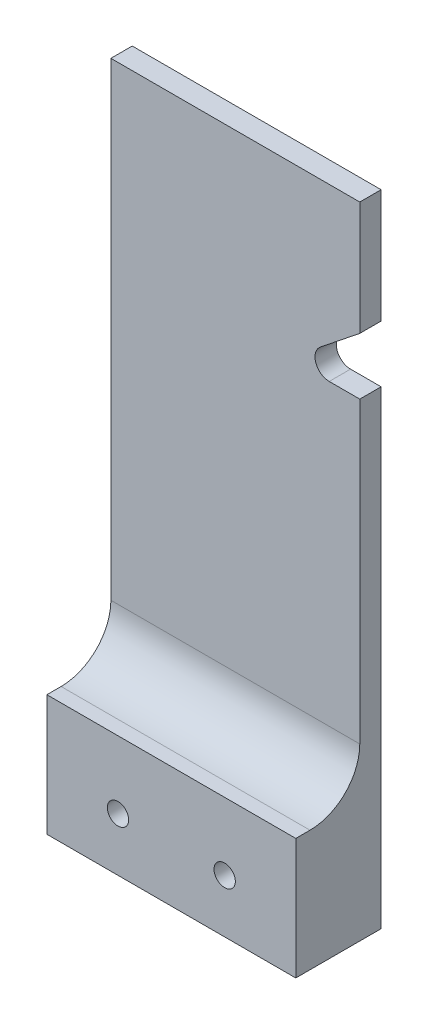
SolidWorks part; units mm, degrees
ref_plane "前视基准面" through (0, 0, 0) normal (0, 0, 1) x (1, 0, 0)
ref_plane "上视基准面" through (0, 0, 0) normal (0, 1, 0) x (1, 0, 0)
ref_plane "右视基准面" through (0, 0, 0) normal (1, 0, 0) x (0, 0, -1)
other "Configuration Table"
sketch "草图1" plane through (0, 0, 0) normal (0, 0, 1) x (1, 0, 0)
  line L1 (-17.5, -45) -> (17.5, -45)
  line L2 (-17.5, -45) -> (-17.5, 45)
  line L3 (-17.5, 45) -> (17.5, 45)
  line L4 (17.5, -45) -> (17.5, 45)
  line L5 (-17.5, -45) -> (17.5, 45) construction
  line L6 (-17.5, 45) -> (17.5, -45) construction
  point P0 (0, 0)
  dimension "D1" = 90
  dimension "D2" = 35
extrude "凸台-拉伸1" add sketch "草图1" along normal blind 3
sketch "草图2" plane through (0, 0, 3) normal (0, 0, 1) x (1, 0, 0)
  line L0 (17.5, -45) -> (17.5, 45) construction
  line L1 (-17.5, -45) -> (17.5, -45)
  line L2 (-17.5, -45) -> (-17.5, -28)
  line L3 (-17.5, -28) -> (17.5, -28)
  line L4 (17.5, -45) -> (17.5, -28)
  dimension "D1" = 17
extrude "凸台-拉伸2" add sketch "草图2" along normal blind 9
fillet "圆角1" radius 7 1 edges at (0, -28, 3)
sketch "草图3" plane through (0, 0, 12) normal (0, 0, 1) x (1, 0, 0)
  line L0 (-17.5, -28) -> (-17.5, -45) construction
  line L1 (17.5, -45) -> (17.5, -28) construction
  line L2 (-17.5, -45) -> (17.5, -45) construction
  circle A0 centre (-7.5, -37.5) radius 1.5
  circle A1 centre (7.5, -37.5) radius 1.5
  dimension "D1" = 3
  dimension "D2" = 3
  dimension "D3" = 10
  dimension "D4" = 10
  dimension "D5" = 7.5
  dimension "D6" = 7.5
extrude "切除-拉伸3" cut sketch "草图3" against normal through all
sketch "草图4" plane through (0, 0, 0) normal (0, 0, -1) x (-1, 0, 0)
  line L0 (-17.5, 29) -> (-17.5, 21)
  line L1 (-17.5, -45) -> (-17.5, 45) construction
  line L2 (-17.5, 21) -> (-7.5, 21)
  line L3 (-7.5, 21) -> (-17.5, 29)
  line L4 (-17.5, 45) -> (17.5, 45) construction
  dimension "D1" = 8
  dimension "D2" = 8
  dimension "D3" = 10
  dimension "D4" = 16
extrude "切除-拉伸4" cut sketch "草图4" against normal through all
fillet "圆角2" radius 2 1 edges at (7.5, 21, 1.5)
